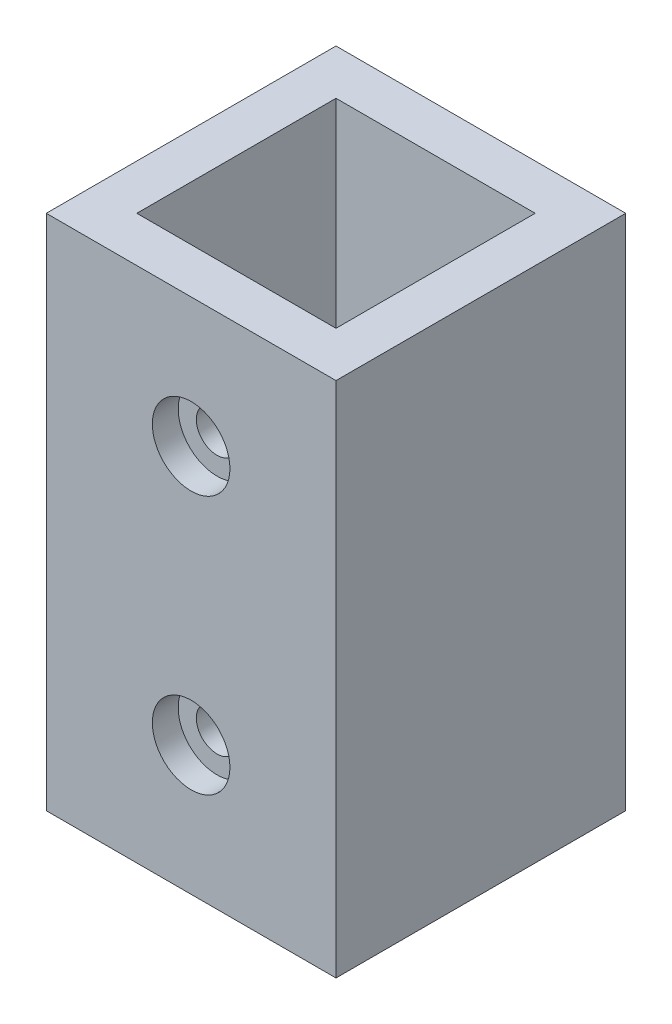
SolidWorks part; units mm, degrees
ref_plane "前视基准面" through (0, 0, 0) normal (0, 0, 1) x (1, 0, 0)
ref_plane "上视基准面" through (0, 0, 0) normal (0, 1, 0) x (1, 0, 0)
ref_plane "右视基准面" through (0, 0, 0) normal (1, 0, 0) x (0, 0, -1)
sketch "草图1" plane through (0, 0, 0) normal (0, 1, 0) x (1, 0, 0)
  line L0 (0, 0) -> (0, 7.7) construction
  line L1 (0, 0) -> (0, -7.7) construction
  line L2 (0, 0) -> (7.7, 0) construction
  line L3 (0, 0) -> (-7.7, 0) construction
  line L4 (0, 7.7) -> (7.7, 7.7)
  line L5 (7.7, 7.7) -> (7.7, 0)
  line L6 (7.7, -7.7) -> (0, -7.7)
  line L7 (-7.7, -7.7) -> (-7.7, 0)
  line L8 (-7.7, 7.7) -> (0, 7.7)
  line L9 (-7.7, 0) -> (-7.7, 7.7)
  line L10 (-7.7, -7.7) -> (0, -7.7)
  line L11 (7.7, -7.7) -> (7.7, 0)
  line L12 (-7.7, -7.7) -> (-7.7, -11.2)
  line L13 (7.7, -7.7) -> (7.7, -11.2)
  line L14 (-7.7, 11.2) -> (-7.7, 7.7)
  line L15 (7.7, 7.7) -> (7.7, 11.2)
  line L19 (-7.7, 11.2) -> (7.7, 11.2)
  line L22 (7.7, -11.2) -> (-7.7, -11.2)
  line L28 (-7.7, -7.7) -> (-4.7, -7.7)
  line L30 (7.7, 11.2) -> (11.2, 11.2)
  line L32 (11.2, 11.2) -> (11.2, -11.2)
  line L33 (7.7, -11.2) -> (11.2, -11.2)
  line L34 (-7.7, -11.2) -> (-11.2, -11.2)
  line L35 (-11.2, -11.2) -> (-11.2, 11.2)
  line L36 (-11.2, 11.2) -> (-7.7, 11.2)
extrude "凸台-拉伸2" add sketch "草图1" along normal blind 3 contours L6 L11 L5 L4 L8 L9 L7 L10 | L8 L4 | L6 L10 region at (0, 0, -9.45) region at (0, 0, 0) region at (0, 0, 9.45)
extrude "凸台-拉伸3" add sketch "草图1<4>" along normal blind 10 separate body contours L22 | L19 region at (0, 0, -9.45) region at (0, 0, 9.45)
sketch "草图1<4>" plane through (0, 0, 0) normal (0, 1, 0) x (1, 0, 0) same geometry as "草图1"
extrude "凸台-拉伸4" add sketch "草图1<5>" along normal blind 40 contours L36 L35 L34 L7 L9 | L33 L32 L30 L5 L11 | L10 | L6 | L4 | L8 region at (0, 0, -9.45) region at (9.45, 0, 0) region at (-9.45, 0, 0) region at (0, 0, 9.45)
sketch "草图1<5>" plane through (0, 0, 0) normal (0, 1, 0) x (1, 0, 0) same geometry as "草图1"
sketch "草图3" plane through (0, 0, -19.6) normal (0, 0, -1) x (-1, 0, 0)
  line L0 (11.2, 13) -> (11.2, 16)
  line L1 (-11.2, 40) -> (-11.2, 0) construction
  line L2 (-11.2, 8) -> (-11.2, 13)
  line L3 (0, 10) -> (0, 30) construction
  line L4 (11.2, 40) -> (11.2, 0) construction
  line L5 (11.2, 8) -> (11.2, 13)
  line L6 (0, 0) -> (0, 10) construction
  line L7 (-11.2, 8) -> (-7.5, 8) construction
  line L8 (11.2, 8) -> (7.5, 8) construction
  line L9 (17.5, 0) -> (-17.5, 0) construction
  circle A0 centre (0, 10) radius 1.6
  circle A1 centre (0, 30) radius 1.6
extrude "切除-拉伸2" cut sketch "草图3" against normal through all contours A0 | A1 region at (0, 10, -19.6) region at (0, 30, -19.6)
sketch "草图10" plane through (0, 0, -11.2) normal (0, 0, -1) x (-1, 0, 0)
  circle A0 centre (0, 30) radius 3
  circle A1 centre (0, 10) radius 3
extrude "切除-拉伸7" cut sketch "草图10" against normal blind 2
sketch "草图11" plane through (0, 0, 11.2) normal (0, 0, 1) x (1, 0, 0)
  circle A0 centre (0, 30) radius 3
  circle A1 centre (0, 10) radius 3
extrude "切除-拉伸8" cut sketch "草图11" against normal blind 2
sketch "草图12" plane through (0, 3, 0) normal (0, 1, 0) x (1, 0, 0)
  line L0 (7.7, 7.7) -> (7.7, -7.7)
  line L1 (7.7, -7.7) -> (-7.7, -7.7)
  line L2 (-7.7, -7.7) -> (-7.7, 7.7)
  line L3 (-7.7, 7.7) -> (7.7, 7.7)
extrude "切除-拉伸9" cut sketch "草图12" against normal through all
